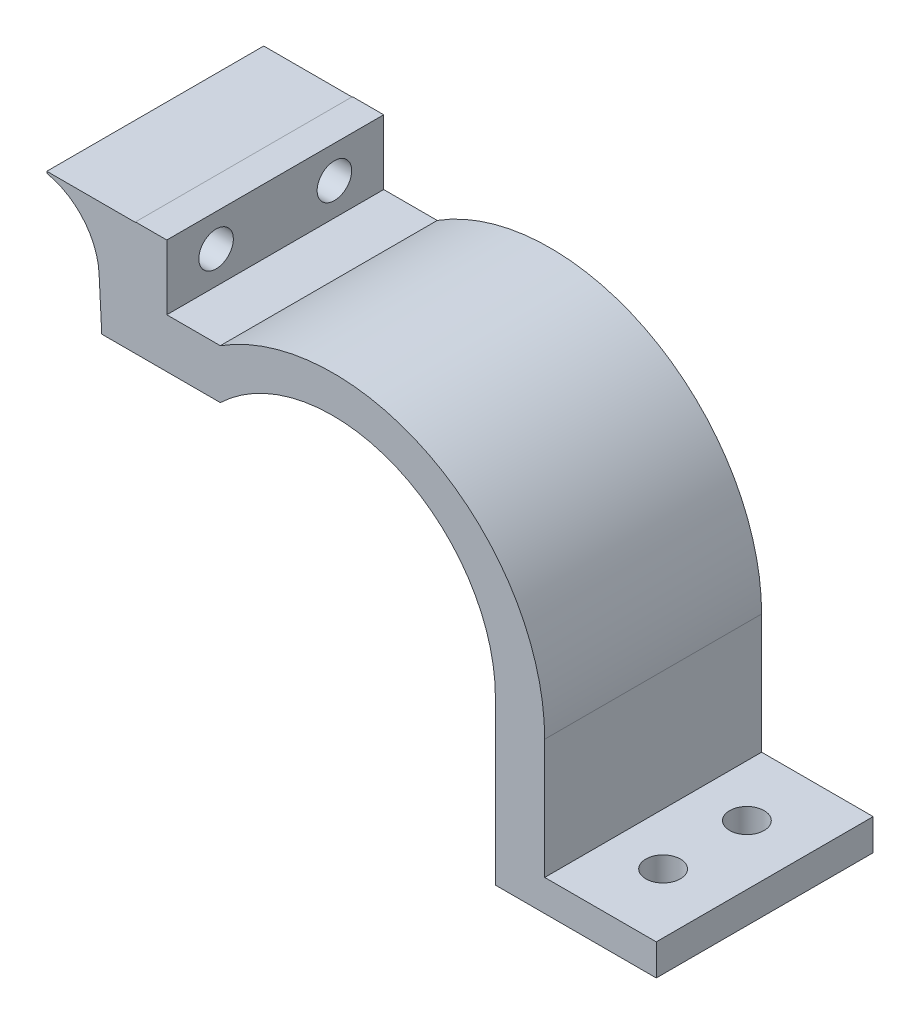
SolidWorks part; units mm, degrees
ref_plane "Front Plane" through (0, 0, 0) normal (0, 0, 1) x (1, 0, 0)
ref_plane "Top Plane" through (0, 0, 0) normal (0, 1, 0) x (1, 0, 0)
ref_plane "Right Plane" through (0, 0, 0) normal (1, 0, 0) x (0, 0, -1)
sketch "Sketch1" plane through (0, 0, 0) normal (0, 0, 1) x (1, 0, 0)
  line L0 (0, 0) -> (33.0033, 0) construction
  line L1 (33.0033, 0) -> (33.0033, -33)
  line L2 (33.0033, -33) -> (0, -33) construction
  line L3 (33.0033, -33) -> (65.6321, -33)
  line L4 (65.6321, -33) -> (65.6321, -26.65)
  line L5 (65.6321, -26.65) -> (43.0033, -26.65)
  line L6 (43.0033, -26.65) -> (43.0033, -2.3696)
  line L7 (0, 0) -> (-40, 0) construction
  line L8 (-40, 0) -> (-40, 50.6526) construction
  line L9 (-22.7938, 23.8598) -> (-40, 23.8598)
  line L10 (-40, 23.8598) -> (-40, 46.9951)
  line L11 (-40, 46.9951) -> (-33.65, 46.9951)
  line L12 (-33.65, 46.9951) -> (-33.65, 33.8598)
  line L13 (-33.65, 33.8598) -> (-22.7938, 33.8598)
  circle A0 centre (0, 0) radius 33 construction
  arc A1 (-22.7938, 23.8598) -> (33.0033, 0) centre (0.0033, 0) cw
  arc A2 (-22.7938, 33.8598) -> (43.0033, -2.3696) centre (0.1304, -2.3696) cw
  dimension "D1" = 10
  dimension "D4" = 33
  dimension "D2" = 6.35
  dimension "D3" = 6.35
  dimension "10" = 10
  dimension "D5" = 40
  dimension "D6" = 32.6288
  dimension "D7" = 23.1354
extrude "Boss-Extrude1" add sketch "Sketch1" against normal blind 44
sketch "Sketch2" plane through (0, -26.65, 0) normal (0, 1, 0) x (1, 0, 0)
  line L0 (53.5164, 34) -> (53.5164, 44) construction
  line L1 (65.6321, 44) -> (43.0033, 44) construction
  line L2 (53.5164, 10) -> (53.5164, 0) construction
  line L3 (65.6321, 0) -> (43.0033, 0) construction
  circle A0 centre (53.5164, 13.5) radius 3.5
  circle A2 centre (53.5164, 30.5) radius 3.5
extrude "Cut-Extrude1" cut sketch "Sketch2" against normal up to next
sketch "Sketch4" plane through (0, 0, 0) normal (0, 0, 1) x (1, 0, 0)
  line L0 (-40, 23.8598) -> (-46.8386, 23.8598)
  line L1 (-47.3809, 34.2065) -> (-44.4795, -21.1542) construction
  line L2 (-46.8386, 23.8598) -> (-47.3809, 34.2065)
  line L4 (-47.3764, 46.9048) -> (-40, 46.9048)
  line L5 (-40, 46.9951) -> (-40, 23.8598) construction
  line L6 (-40, 46.9048) -> (-40, 23.8598)
  line L7 (-47.3764, 46.9048) -> (-57.9858, 46.9048)
  line L8 (-57.9858, 46.9048) -> (-57.9858, 46.5446)
  arc A0 (-57.9858, 46.5446) -> (-47.3809, 34.2065) centre (-60.6709, 33.51) cw
extrude "Boss-Extrude2" add sketch "Sketch4" against normal up to surface (44 mm away) up to face at (9.0807, 10.4678, -44)
sketch "Sketch5" plane through (-33.65, 0, 0) normal (1, 0, 0) x (0, 0, -1)
  line L0 (0, 33.8598) -> (0, 46.9951) construction
  line L1 (44, 33.8598) -> (44, 46.9951) construction
  line L2 (44, 46.9951) -> (0, 46.9951) construction
  circle A0 centre (10, 40.4251) radius 3.5
  circle A1 centre (34, 40.4251) radius 3.5
  dimension "D1" = 7
  dimension "D2" = 7
  dimension "D3" = 10
  dimension "D4" = 10
  dimension "D5" = 6.57
extrude "Cut-Extrude2" cut sketch "Sketch5" against normal up to next
ref_plane "Plane1" through (-58.65, 0, 0) normal (1, 0, 0) x (0, 0, -1)
sketch "Sketch6" plane through (-58.65, 0, 0) normal (1, 0, 0) x (0, 0, -1)
  circle A0 centre (34, 40.4251) radius 5
  circle A1 centre (10, 40.4251) radius 5
  dimension "D1" = 10
extrude "Cut-Extrude3" cut sketch "Sketch6" along normal blind 15
